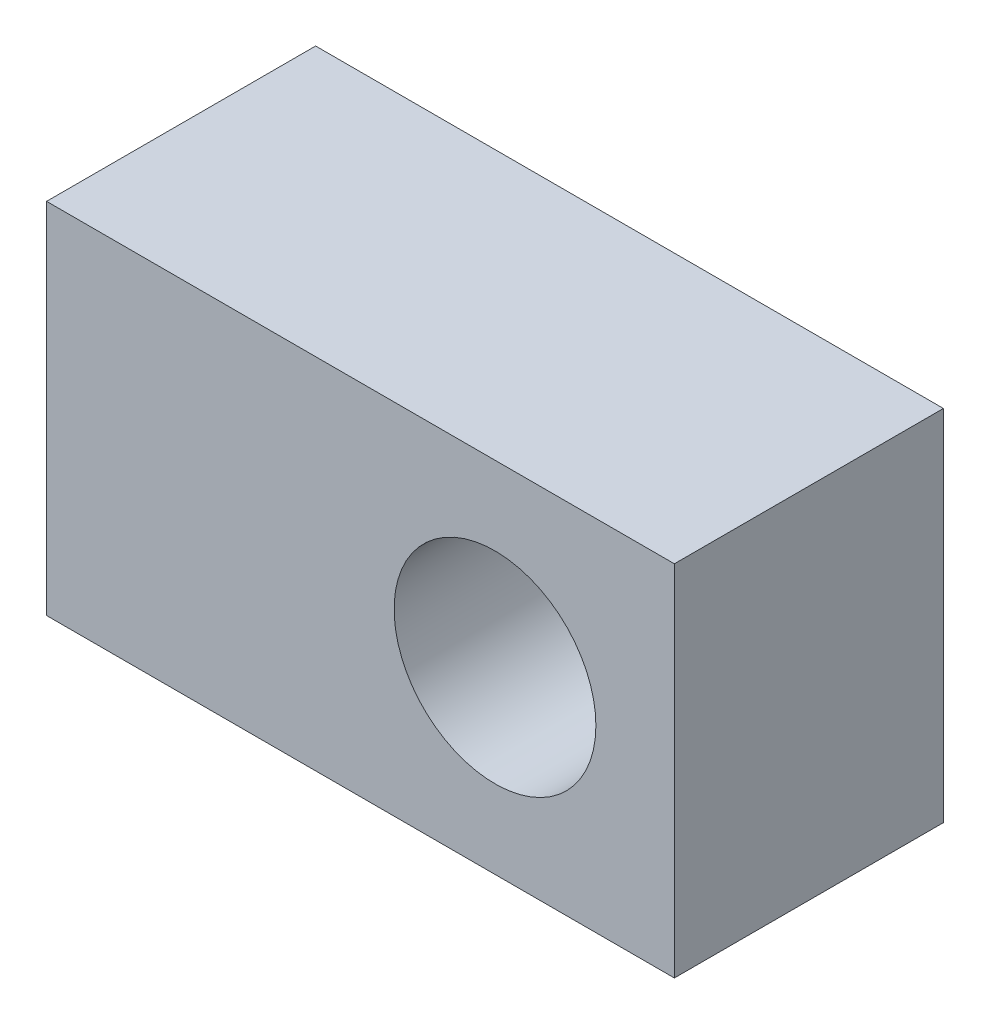
SolidWorks part; units mm, degrees
ref_plane "Front Plane" through (0, 0, 0) normal (0, 0, 1) x (1, 0, 0)
ref_plane "Top Plane" through (0, 0, 0) normal (0, 1, 0) x (1, 0, 0)
ref_plane "Right Plane" through (0, 0, 0) normal (1, 0, 0) x (0, 0, -1)
sketch "Sketch2" plane through (0, 0, 0) normal (0, 0, 1) x (1, 0, 0)
  line L1 (0, 0) -> (88.9, 0)
  line L2 (0, 0) -> (0, 50.8)
  line L3 (0, 50.8) -> (88.9, 50.8)
  line L4 (88.9, 0) -> (88.9, 50.8)
  dimension "D1" = 88.9
  dimension "D2" = 50.8
extrude "Boss-Extrude1" add sketch "Sketch2" along normal blind 38.1
sketch "Sketch3" plane through (0, 0, 38.1) normal (0, 0, 1) x (1, 0, 0)
  line L0 (88.9, 0) -> (88.9, 50.8) construction
  circle A0 centre (63.5, 25.4) radius 14.2875
  dimension "D1" = 28.575
  dimension "D2" = 25.4
extrude "Cut-Extrude1" cut sketch "Sketch3" against normal through all and the other way through all
sketch "Sketch4" plane through (0, 0, 0) normal (-1, 0, 0) x (0, 0, 1)
  line L0 (38.1, 50.8) -> (38.1, 0) construction
  circle A0 centre (19.05, 25.4) radius 12.7
  dimension "D1" = 25.4
  dimension "D2" = 19.05
extrude "Cut-Extrude2" cut sketch "Sketch4" against normal blind 38.1
